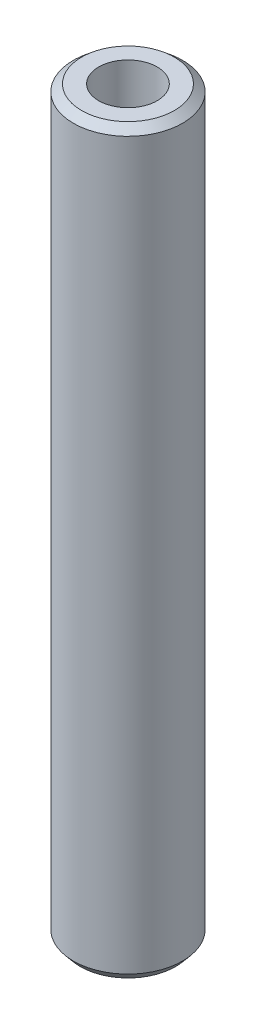
SolidWorks part; units mm, degrees
ref_plane "Front Plane" through (0, 0, 0) normal (0, 0, 1) x (1, 0, 0)
ref_plane "Top Plane" through (0, 0, 0) normal (0, 1, 0) x (1, 0, 0)
ref_plane "Right Plane" through (0, 0, 0) normal (1, 0, 0) x (0, 0, -1)
sketch "Sketch1" plane through (0, 0, 0) normal (0, 1, 0) x (1, 0, 0)
  circle A0 centre (0, 0) radius 42.5
  dimension "SHAFT_OD" = 85
extrude "Boss-Extrude1" add sketch "Sketch1" along normal blind 576.6649
sketch "Sketch2" plane through (0, 0, 0) normal (0, 1, 0) x (1, 0, 0)
  circle A0 centre (0, 0) radius 22.7875
  dimension "BORE_D" = 45.5751
extrude "Cut-Extrude1" cut sketch "Sketch2" along normal through all
chamfer "Chamfer1" distance 5.3587 angle 50.186 2 edges at (0, 576.6649, 42.5) (0, 0, 42.5) first distance on face at (0, 576.6649, 42.5) first distance on face at (0, 0, 22.7875)
